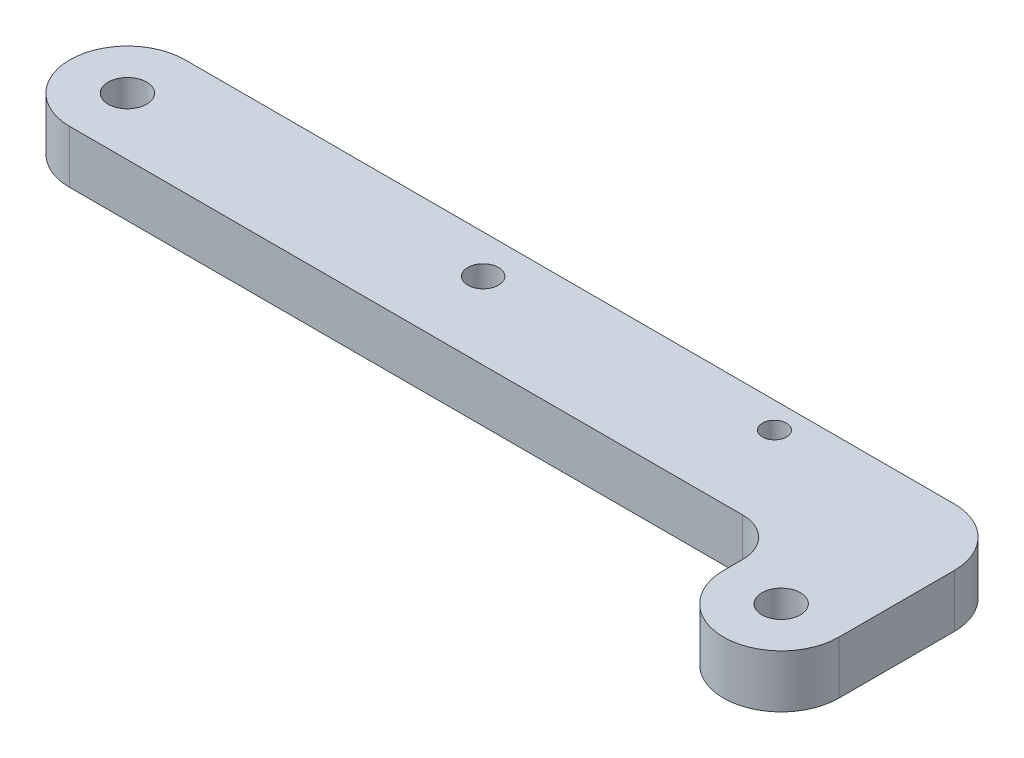
SolidWorks part; units mm, degrees
ref_plane "正面" through (0, 0, 0) normal (0, 0, 1) x (1, 0, 0)
ref_plane "平面" through (0, 0, 0) normal (0, 1, 0) x (1, 0, 0)
ref_plane "右側面" through (0, 0, 0) normal (1, 0, 0) x (0, 0, -1)
sketch "ｽｹｯﾁ1" plane through (0, 0, 0) normal (0, 1, 0) x (1, 0, 0)
  line L0 (0, 0) -> (80, 0) construction
  line L1 (0, 6) -> (80, 6)
  line L2 (0, -6) -> (80, -6)
  arc A0 (0, 6) -> (0, -6) centre (0, 0) ccw
  arc A1 (80, -6) -> (80, 6) centre (80, 0) ccw
  circle A2 centre (0, 0) radius 2
  circle A3 centre (80, 0) radius 2 construction
  circle A4 centre (64, 3.3) radius 1.25
  point P3 (40, 0)
  dimension "D2" = 6
  dimension "D3" = 4
  dimension "D4" = 4
  dimension "D7" = 2.5
  dimension "D1" = 80
  dimension "D5" = 64
  dimension "D6" = 2.7
extrude "ﾎﾞｽ - 押し出し1" add sketch "ｽｹｯﾁ1" along normal blind 5.5
sketch "ｽｹｯﾁ3" plane through (0, 5.5, 0) normal (0, 1, 0) x (1, 0, 0)
  line L0 (80, 0) -> (80, -12) construction
  line L1 (86, 0) -> (86, -12)
  line L2 (74, 0) -> (74, -12)
  line L3 (0, -6) -> (80, -6) construction
  arc A0 (86, 0) -> (74, 0) centre (80, 0) ccw
  arc A1 (74, -12) -> (86, -12) centre (80, -12) ccw
  arc A2 (80, -6) -> (80, 6) centre (80, 0) ccw construction
  circle A3 centre (80, -12) radius 2
  point P3 (80, -6)
  dimension "D1" = 4
extrude "ﾎﾞｽ - 押し出し3" add sketch "ｽｹｯﾁ3" against normal up to surface (5.5 mm away) up to face at (40, 0, 0)
fillet "ﾌｨﾚｯﾄ1" radius 4 1 edges at (74, 2.75, 6)
sketch "ｽｹｯﾁ4" plane through (0, 5.5, 0) normal (0, 1, 0) x (1, 0, 0)
  line L1 (80, 6) -> (0, 6) construction
  circle A0 centre (35, 2) radius 1.6
  circle A1 centre (80, -12) radius 2 construction
  dimension "D1" = 3.2
  dimension "D2" = 45
  dimension "D3" = 4
extrude "ｶｯﾄ - 押し出し1" cut sketch "ｽｹｯﾁ4" against normal blind 10
